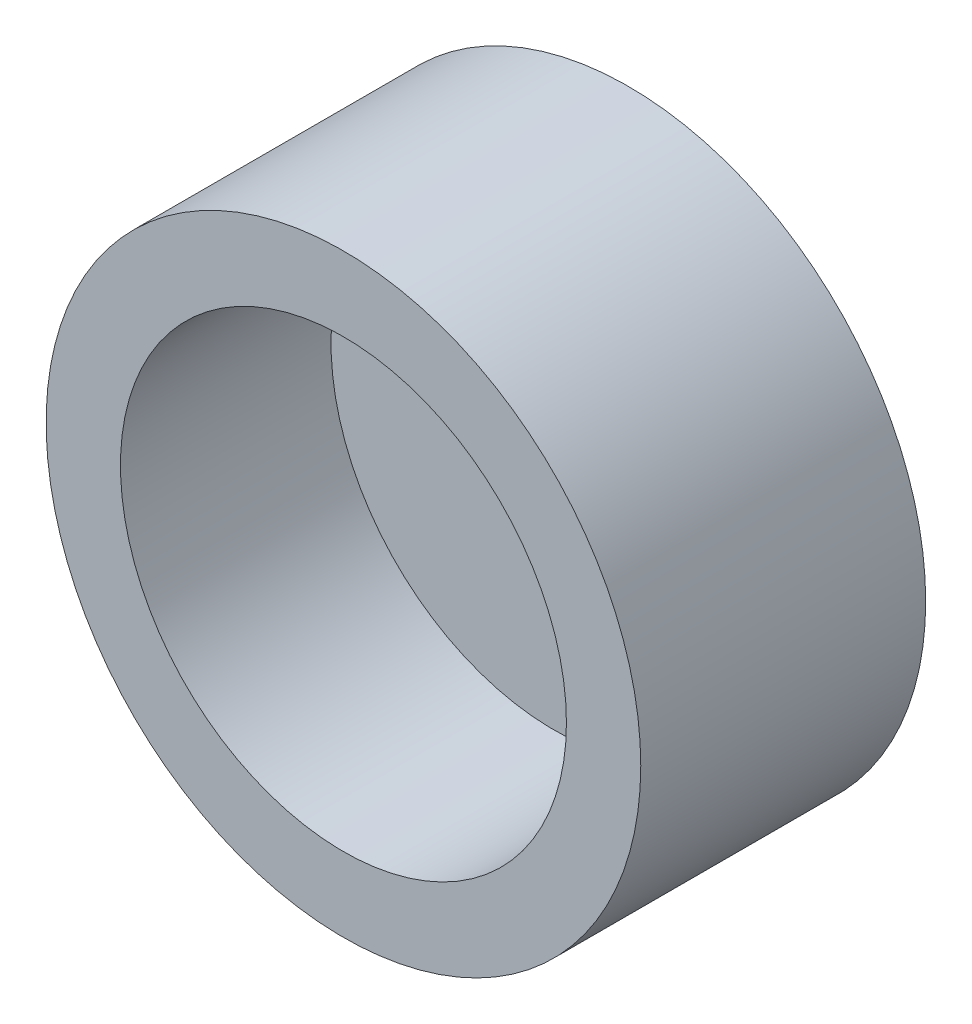
SolidWorks part; units mm, degrees
ref_plane "Front Plane" through (0, 0, 0) normal (0, 0, 1) x (1, 0, 0)
ref_plane "Top Plane" through (0, 0, 0) normal (0, 1, 0) x (1, 0, 0)
ref_plane "Right Plane" through (0, 0, 0) normal (1, 0, 0) x (0, 0, -1)
sketch "Sketch1" plane through (0, 0, 0) normal (0, 0, 1) x (1, 0, 0)
  circle A0 centre (0, 0) radius 9
  circle A1 centre (0, 0) radius 12
  dimension "D1" = 3
  dimension "D2" = 18
extrude "Boss-Extrude1" add sketch "Sketch1" along normal blind 8.5
extrude "Boss-Extrude2" add sketch "Sketch1<2>" against normal blind 3 contours A1
sketch "Sketch1<2>" plane through (0, 0, 0) normal (0, 0, 1) x (1, 0, 0) same geometry as "Sketch1"
sketch "Sketch2" plane through (0, 0, -3) normal (0, 0, -1) x (-1, 0, 0)
  circle A0 centre (0, 0) radius 3.5
  dimension "D1" = 7
extrude "Cut-Extrude1" cut sketch "Sketch2" against normal blind 2.5
